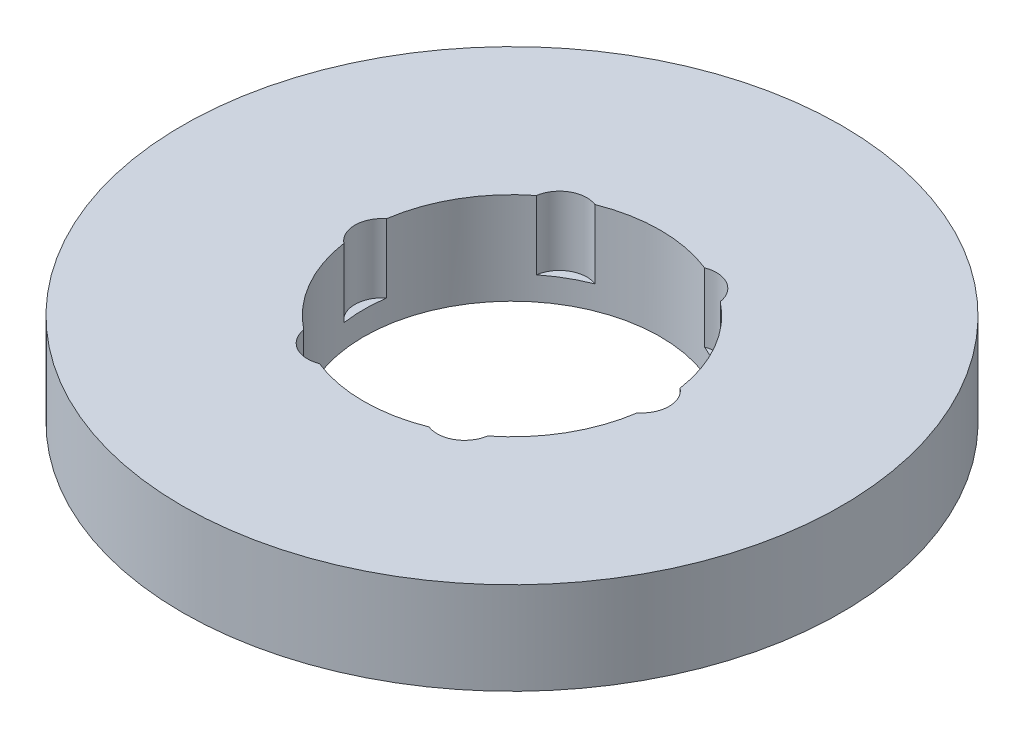
SolidWorks part; units mm, degrees
ref_plane "Front Plane" through (0, 0, 0) normal (0, 0, 1) x (1, 0, 0)
ref_plane "Top Plane" through (0, 0, 0) normal (0, 1, 0) x (1, 0, 0)
ref_plane "Right Plane" through (0, 0, 0) normal (1, 0, 0) x (0, 0, -1)
sketch "Sketch1" plane through (0, 0, 0) normal (0, 1, 0) x (1, 0, 0)
  circle A0 centre (0, 0) radius 100
  dimension "FLANGE_OD" = 200
extrude "Boss-Extrude1" add sketch "Sketch1" along normal blind 28
sketch "Sketch2" plane through (0, 0, 0) normal (0, 1, 0) x (1, 0, 0)
  circle A0 centre (0, 0) radius 45
  dimension "BORE_D" = 90
extrude "Cut-Extrude1" cut sketch "Sketch2" along normal through all
sketch "Sketch3" plane through (0, 28, 0) normal (0, 1, 0) x (1, 0, 0)
  circle A0 centre (0, 0) radius 39.3413 construction
  circle A1 centre (-39.3413, 0) radius 8.3105
  dimension "BOLT_D" = 16.6209
  dimension "BOLT_PCD" = 78.6825
extrude "Cut-Extrude2" cut sketch "Sketch3" against normal blind 20.8502
pattern_circular "CirPattern1" count 6 over 360 about axis through (0, 0, 0) along (0, 1, 0) of "Cut-Extrude2"
